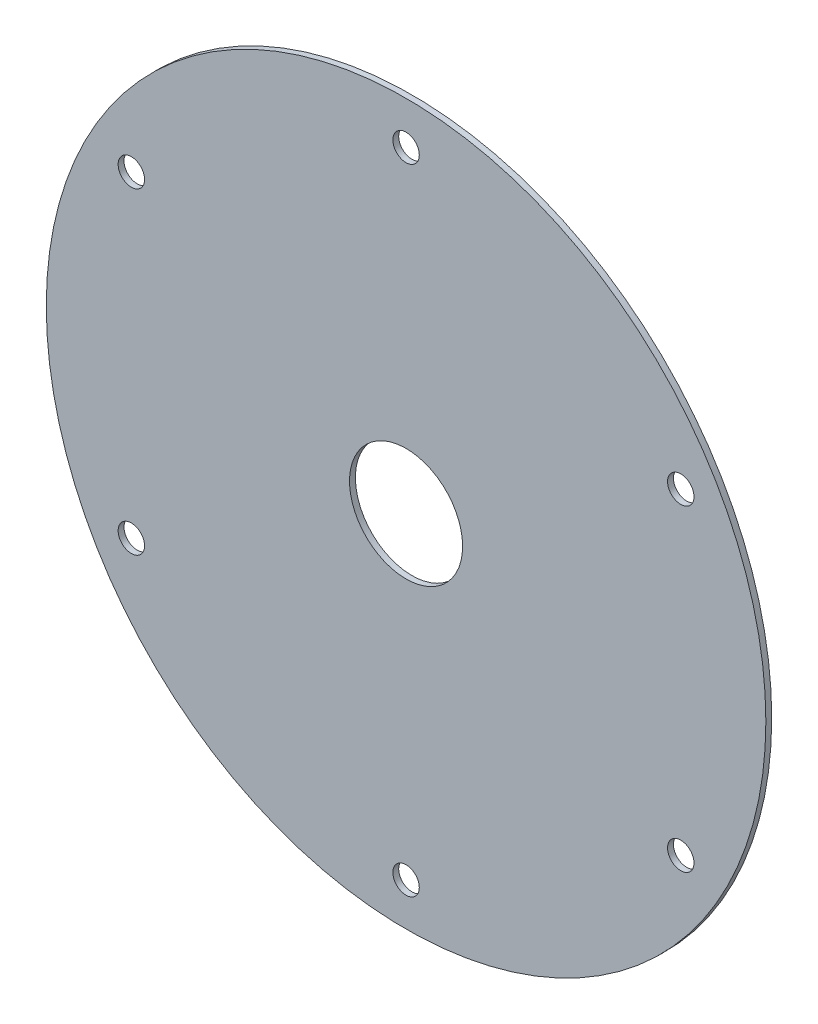
SolidWorks part; units mm, degrees
material "СТ3КП"
ref_plane "Спереди" through (0, 0, 0) normal (0, 0, 1) x (1, 0, 0)
ref_plane "Сверху" through (0, 0, 0) normal (0, 1, 0) x (1, 0, 0)
ref_plane "Справа" through (0, 0, 0) normal (1, 0, 0) x (0, 0, -1)
sketch "Эскиз1" plane through (0, 0, 0) normal (0, 0, 1) x (1, 0, 0)
  line L0 (0, 0) -> (0, 225) construction
  line L1 (0, 0) -> (0, 216) construction
  line L2 (0, 0) -> (187.0615, 108) construction
  line L3 (187.0615, 108) -> (0, 216) construction
  circle A0 centre (0, 0) radius 245
  circle A1 centre (0, 0) radius 38.5 construction
  circle A2 centre (0, 0) radius 38.5
  circle A3 centre (0, 216) radius 9
  circle A4 centre (187.0615, 108) radius 9
  circle A5 centre (187.0615, -108) radius 9
  circle A6 centre (0, -216) radius 9
  circle A7 centre (-187.0615, -108) radius 9
  circle A8 centre (-187.0615, 108) radius 9
  point P0 (97.1179, 41.7894)
  point P14 (0, 0)
  point P25 (0, 0)
  dimension "D1" = 6
base flange "Базовая кромка1" sketch "Эскиз1" thickness 4 reverse thickness direction yes parameters "D1"=1.5
sketch "Сгиб-Линии1" plane through (0, 0, 0) normal (0, 1, 0) x (1, 0, 0)
sketch "Граничная рамка1" plane through (0, 0, 0) normal (0, 1, 0) x (1, 0, 0)
sheet metal parameters "Листовой металл3" thickness 4 parameters "D1"=1.5
flat pattern "Развертка3" [suppressed]
sketch "Сгиб-Линии2" plane through (0, 0, 0) normal (0, 1, 0) x (1, 0, 0)
sketch "Граничная рамка2" [suppressed] plane through (0, 0, 0) normal (0, 1, 0) x (1, 0, 0)
